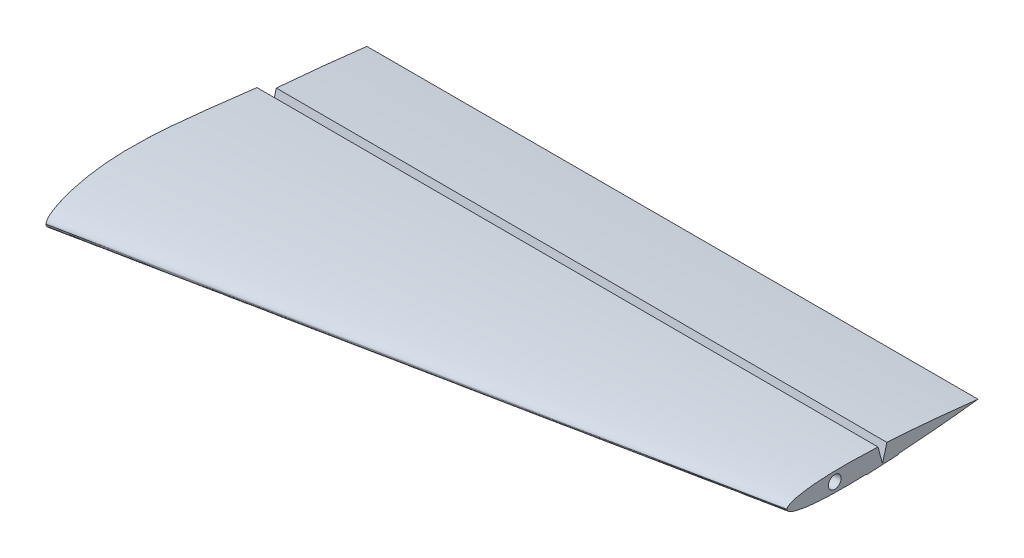
SolidWorks part; units mm, degrees
ref_plane "Front Plane" through (0, 0, 0) normal (0, 0, 1) x (1, 0, 0)
ref_plane "Top Plane" through (0, 0, 0) normal (0, 1, 0) x (1, 0, 0)
ref_plane "Right Plane" through (0, 0, 0) normal (1, 0, 0) x (0, 0, -1)
sketch "0010 template"
sketch_block_instance "Block2-1"
sketch_block "Block2"
sketch "Sketch4" plane through (0, 0, 0) normal (1, 0, 0) x (0, 0, -1)
  line L0 (0, 0) -> (-250, 0) construction
  spline S0 degree 4 poles (-250, 0) (-249.9999, 0.1958) (-249.9612, 0.6039) (-249.7596, 1.2633) (-249.1282, 2.2398) (-248.1098, 3.1752) (-246.5761, 4.1828) (-244.1271, 5.3667) (-240.0739, 6.8179) (-232.84, 8.6113) (-221.2945, 10.4497) (-205.8077, 11.8178) (-187.4923, 12.5325) (-167.6157, 12.5624) (-147.9613, 12.1042) (-127.9831, 11.2209) (-108.5655, 10.1073) (-88.2725, 8.6479) (-69.4578, 7.1641) (-48.2492, 5.205) (-31.0441, 3.5474) (-5.6278, 0.7144) (5.3818, -0.6305) (19.3913, -2.4508) (24.9342, -3.2323) knots 0 0 0 0 0 0.002791 0.005883 0.009735 0.016522 0.022438 0.032158 0.048634 0.078249 0.129037 0.199997 0.270957 0.341918 0.412878 0.483838 0.554798 0.625759 0.696719 0.767679 0.83864 0.9096 1 1 1 1 1 construction
  spline S1 degree 4 poles (-250, 0) (-249.9999, 0.1958) (-249.9612, 0.6039) (-249.7596, 1.2633) (-249.1282, 2.2398) (-248.1098, 3.1752) (-246.5761, 4.1828) (-244.1271, 5.3667) (-240.0739, 6.8179) (-232.84, 8.6113) (-221.2945, 10.4497) (-205.8077, 11.8178) (-187.4923, 12.5325) (-167.6157, 12.5624) (-147.9613, 12.1042) (-127.9831, 11.2209) (-108.5655, 10.1073) (-88.2725, 8.6479) (-69.4578, 7.1641) (-48.2492, 5.205) (-31.0441, 3.5474) (-13.2038, 1.5588) (-4.4672, 0.5411) (0, 0) knots 0 0 0 0 0 0.002791 0.005883 0.009735 0.016522 0.022438 0.032158 0.048634 0.078249 0.129037 0.199997 0.270957 0.341918 0.412878 0.483838 0.554798 0.625759 0.696719 0.767679 0.83864 0.9096 0.9096 0.9096 0.9096 0.9096
  spline S2 degree 4 poles (-250, 0) (-249.9999, -0.1958) (-249.9612, -0.6039) (-249.7596, -1.2633) (-249.1282, -2.2398) (-248.1098, -3.1752) (-246.5761, -4.1828) (-244.1271, -5.3667) (-240.0739, -6.8179) (-232.84, -8.6113) (-221.2945, -10.4497) (-205.8077, -11.8178) (-187.4923, -12.5325) (-167.6157, -12.5624) (-147.9613, -12.1042) (-127.9831, -11.2209) (-108.5655, -10.1073) (-88.2725, -8.6479) (-69.4578, -7.1641) (-48.2492, -5.205) (-31.0441, -3.5474) (-13.2038, -1.5588) (-4.4672, -0.5411) (0, 0) knots 0 0 0 0 0 0.002791 0.005883 0.009735 0.016522 0.022438 0.032158 0.048634 0.078249 0.129037 0.199997 0.270957 0.341918 0.412878 0.483838 0.554798 0.625759 0.696719 0.767679 0.83864 0.9096 0.9096 0.9096 0.9096 0.9096
ref_plane "Plane1" through (500, 0, 0) normal (1, 0, 0) x (0, 0, -1)
sketch "Sketch7" plane through (500, 0, 0) normal (1, 0, 0) x (0, 0, -1)
  line L0 (0, 0) -> (-150, 0) construction
  spline S0 degree 4 poles (-150, 0) (-149.9999, 0.1175) (-149.9767, 0.3624) (-149.8557, 0.758) (-149.4769, 1.3439) (-148.8659, 1.9051) (-147.9457, 2.5097) (-146.4763, 3.22) (-144.0443, 4.0908) (-139.704, 5.1668) (-132.7767, 6.2698) (-123.4846, 7.0907) (-112.4954, 7.5195) (-100.5694, 7.5374) (-88.7768, 7.2625) (-76.7899, 6.7325) (-65.1393, 6.0644) (-52.9635, 5.1887) (-41.6747, 4.2985) (-28.9495, 3.123) (-18.6265, 2.1284) (-3.3767, 0.4286) (3.2291, -0.3783) (11.6348, -1.4705) (14.9605, -1.9394) knots 0 0 0 0 0 0.002791 0.005883 0.009735 0.016522 0.022438 0.032158 0.048634 0.078249 0.129037 0.199997 0.270957 0.341918 0.412878 0.483838 0.554798 0.625759 0.696719 0.767679 0.83864 0.9096 1 1 1 1 1 construction
  spline S1 degree 4 poles (-150, 0) (-149.9999, 0.1175) (-149.9767, 0.3624) (-149.8557, 0.758) (-149.4769, 1.3439) (-148.8659, 1.9051) (-147.9457, 2.5097) (-146.4763, 3.22) (-144.0443, 4.0908) (-139.704, 5.1668) (-132.7767, 6.2698) (-123.4846, 7.0907) (-112.4954, 7.5195) (-100.5694, 7.5374) (-88.7768, 7.2625) (-76.7899, 6.7325) (-65.1393, 6.0644) (-52.9635, 5.1887) (-41.6747, 4.2985) (-28.9495, 3.123) (-18.6265, 2.1284) (-7.9223, 0.9353) (-2.6803, 0.3247) (0, 0) knots 0 0 0 0 0 0.002791 0.005883 0.009735 0.016522 0.022438 0.032158 0.048634 0.078249 0.129037 0.199997 0.270957 0.341918 0.412878 0.483838 0.554798 0.625759 0.696719 0.767679 0.83864 0.9096 0.9096 0.9096 0.9096 0.9096
  spline S2 degree 4 poles (-150, 0) (-149.9999, -0.1175) (-149.9767, -0.3624) (-149.8557, -0.758) (-149.4769, -1.3439) (-148.8659, -1.9051) (-147.9457, -2.5097) (-146.4763, -3.22) (-144.0443, -4.0908) (-139.704, -5.1668) (-132.7767, -6.2698) (-123.4846, -7.0907) (-112.4954, -7.5195) (-100.5694, -7.5374) (-88.7768, -7.2625) (-76.7899, -6.7325) (-65.1393, -6.0644) (-52.9635, -5.1887) (-41.6747, -4.2985) (-28.9495, -3.123) (-18.6265, -2.1284) (-7.9223, -0.9353) (-2.6803, -0.3247) (0, 0) knots 0 0 0 0 0 0.002791 0.005883 0.009735 0.016522 0.022438 0.032158 0.048634 0.078249 0.129037 0.199997 0.270957 0.341918 0.412878 0.483838 0.554798 0.625759 0.696719 0.767679 0.83864 0.9096 0.9096 0.9096 0.9096 0.9096
  dimension "D1" = 0
loft "Loft2" add profiles "Sketch7", "Sketch4" connector at (500, 0, 150) connector at (0, 0, 250)
sketch "Sketch8" plane through (0, 0, 0) normal (-1, 0, 0) x (0, 0, 1)
  line L0 (0, 0) -> (250, 0) construction
  line L1 (75, 0) -> (75, -7.293) construction
  line L2 (75, -7.293) -> (70.1733, 10.7205)
  line L3 (70.1733, 10.7205) -> (79.8267, 10.7205)
  line L4 (79.8267, 10.7205) -> (75, -7.293)
  dimension "D1" = 75
  dimension "D2" = 15
  dimension "D3" = 15
sketch "Sketch9" plane through (500, 0, 0) normal (1, 0, 0) x (0, 0, -1)
  line L0 (-150, 0) -> (0, 0) construction
  line L1 (-75, 0) -> (-75, -6.3837) construction
  line L2 (-75, -6.3837) -> (-79.0924, 8.8893)
  line L3 (-79.0924, 8.8893) -> (-70.9076, 8.8893)
  line L4 (-70.9076, 8.8893) -> (-75, -6.3837)
  dimension "D1" = 15
  dimension "D2" = 15
  dimension "D3" = 75
loft "Cut-Loft1" cut profiles "Sketch9", "Sketch8" connector at (500, 8.8893, 70.9076) connector at (0, 10.7205, 70.1733)
sketch "Sketch12" plane through (0, 0, 0) normal (-1, 0, 0) x (0, 0, 1)
  line L0 (137.5, 0) -> (-137.5, 0) construction
  point P0 (187.5, 0)
  dimension "D1" = 62.5
sketch "Sketch13" plane through (500, 0, 0) normal (1, 0, 0) x (0, 0, -1)
  line L0 (137.5, 0) -> (-137.5, 0) construction
  point P0 (-112.5, 0)
  dimension "D1" = 37.5
ref_axis "Axis1" through (500, 0, 112.5) along (-0.9889, 0, 0.1483)
ref_plane "Plane2" through (500, 0, 112.5) normal (-0.9889, 0, 0.1483) x (0.1483, 0, 0.9889)
sketch "Sketch14" plane through (500, 0, 112.5) normal (-0.9889, 0, 0.1483) x (0.1483, 0, 0.9889)
  circle A0 centre (0, 0) radius 5
  dimension "D1" = 10
extrude "Cut-Extrude3" cut sketch "Sketch14" against normal through all and the other way through all
sketch "Sketch10" plane through (0, 0, 0) normal (0, 1, 0) x (1, 0, 0)
  line L0 (500, 0) -> (0, 0) construction
  line L1 (20, 0) -> (0, 0)
  line L2 (20, 0) -> (20, -79.0722)
  line L3 (20, -79.0722) -> (0, -79.0722)
  line L4 (0, 0) -> (0, -79.0722)
  line L5 (0, -13.8186) -> (0, 13.8186) construction
  spline S0 degree 3 poles (500, -78.5288) (416.6672, -78.6598) (333.3338, -78.7555) (166.667, -78.9261) (83.3335, -79.0019) (0, -79.0722) knots 0 0 0 0 0.5 0.5 1 1 1 1 construction
  dimension "D1" = 20
extrude "Cut-Extrude1" cut sketch "Sketch10" against normal through all and the other way through all
sketch "Sketch11" plane through (0, 0, 0) normal (0, 0, 1) x (1, 0, 0)
  circle A0 centre (0, 0) radius 15
  dimension "D1" = 30
extrude "Cut-Extrude2" cut sketch "Sketch11" along normal through all
ref_axis "Axis2" through (20, -7.2566, 75) along (1, 0.0018, 0)
sketch "Sketch16" plane through (0, 0, 0) normal (0, 1, 0) x (1, 0, 0)
  line L0 (20, -75) -> (500, -75) construction
  line L1 (30, -95) -> (74, -95)
  line L2 (30, -95) -> (30, -139)
  line L3 (30, -139) -> (74, -139)
  line L4 (74, -95) -> (74, -139)
  dimension "D1" = 44
  dimension "D2" = 44
  dimension "D3" = 20
  dimension "D4" = 10
extrude "Cut-Extrude4" cut sketch "Sketch16" against normal through all and the other way blind 5.2
sketch "Sketch17" plane through (500, 0, 0) normal (1, 0, 0) x (0, 0, -1)
  line L0 (-87.4762, -7.1658) -> (-62.4762, -5.8528)
  line L1 (-62.4762, -5.8528) -> (-62.4499, -6.3521)
  line L2 (-62.4499, -6.3521) -> (-87.4499, -7.6651)
  line L3 (-87.4499, -7.6651) -> (-87.4762, -7.1658)
  spline S0 degree 4 poles (-150, 0) (-149.9999, -0.1175) (-149.9767, -0.3624) (-149.8557, -0.758) (-149.4769, -1.3439) (-148.8659, -1.9051) (-147.9457, -2.5097) (-146.4763, -3.22) (-144.0443, -4.0908) (-139.704, -5.1668) (-132.7767, -6.2698) (-123.4846, -7.0907) (-112.4954, -7.5195) (-100.5694, -7.5374) (-88.7768, -7.2625) (-76.7899, -6.7325) (-65.1393, -6.0644) (-52.9635, -5.1887) (-41.6747, -4.2985) (-28.9495, -3.123) (-18.6265, -2.1284) (-7.9223, -0.9353) (-2.6803, -0.3247) (0, 0) knots 0 0 0 0 0 0.002791 0.005883 0.009735 0.016522 0.022438 0.032158 0.048634 0.078249 0.129037 0.199997 0.270957 0.341918 0.412878 0.483838 0.554798 0.625759 0.696719 0.767679 0.83864 0.9096 0.9096 0.9096 0.9096 0.9096 construction
  dimension "D1" = 12.5
  dimension "D2" = 25
  dimension "D3" = 25
  dimension "D4" = 0.5
sketch "Sketch18" plane through (20, 0, 0) normal (-1, 0, 0) x (0, 0, 1)
  line L0 (62.5206, -6.4867) -> (87.5206, -8.5898)
  line L1 (87.5206, -8.5898) -> (87.4786, -9.0898)
  line L2 (87.4786, -9.0898) -> (62.4786, -6.9867)
  line L3 (62.4786, -6.9867) -> (62.5206, -6.4867)
  spline S0 degree 4 poles (0, 0) (4.3957, -0.5324) (12.9925, -1.5339) (30.5474, -3.4906) (47.4772, -5.1218) (63.5399, -6.6055) (73.5371, -7.4389) (78.6958, -7.8492) (79.0722, -7.8791) knots 0 0 0 0 0 0.078013 0.156025 0.234038 0.312051 0.318192 0.318192 0.318192 0.318192 0.318192 construction
  dimension "D1" = 12.5
  dimension "D2" = 0.5
  dimension "D3" = 25
loft "Loft3" add profiles "Sketch18", "Sketch17" connector at (20, -9.0898, 87.4786) connector at (500, -7.6651, 87.4499)
